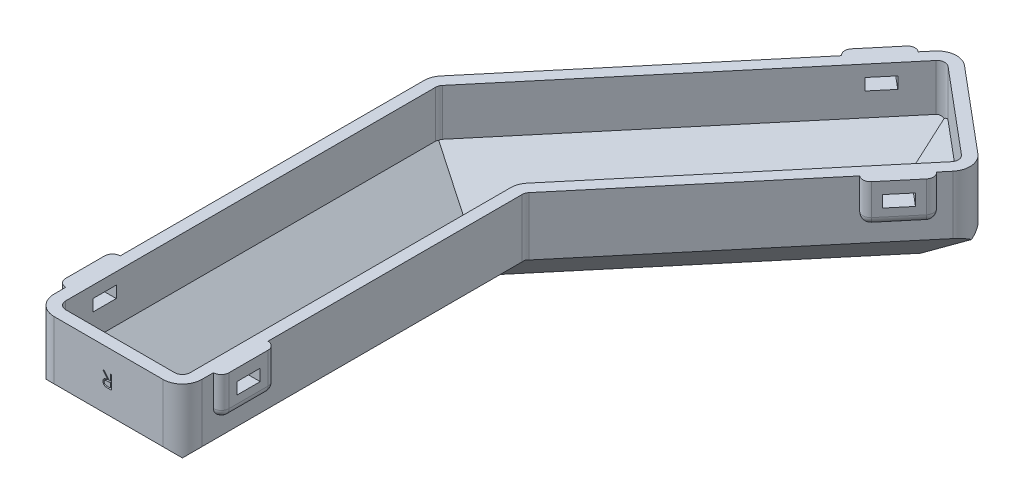
SolidWorks part; units mm, degrees
ref_plane "Front Plane" through (0, 0, 0) normal (0, 0, 1) x (1, 0, 0)
ref_plane "Top Plane" through (0, 0, 0) normal (0, 1, 0) x (1, 0, 0)
ref_plane "Right Plane" through (0, 0, 0) normal (1, 0, 0) x (0, 0, -1)
sketch "Sketch1" plane through (0, 0, 0) normal (0, 1, 0) x (1, 0, 0)
  line L0 (0, -95) -> (0, 0) construction
  line L1 (0, 0) -> (57.8509, 68.944) construction
  line L2 (19, -95) -> (19, -6.9154)
  line L3 (-19, -95) -> (-19, 6.9154)
  line L4 (-19, -95) -> (19, -95)
  line L5 (19, -6.9154) -> (72.4057, 56.731)
  line L6 (43.296, 81.157) -> (72.4057, 56.731)
  line L7 (43.296, 81.157) -> (-19, 6.9154)
  line L8 (43.6658, 76.9305) -> (68.1792, 56.3613) construction
  line L9 (43.6658, 76.9305) -> (-16, 5.8235) construction
  line L10 (-16, 5.8235) -> (-16, -92) construction
  line L11 (-16, -92) -> (16, -92) construction
  line L12 (16, -92) -> (16, -5.8235) construction
  line L13 (16, -5.8235) -> (68.1792, 56.3613) construction
  point P9 (0, -95)
  point P10 (57.8509, 68.944)
  point P12 (55.9225, 66.6459)
  point P13 (0, -92)
  dimension "D1" = 95
  dimension "D2" = 90
  dimension "D3" = 38
  dimension "D4" = 38
  dimension "D5" = 140
  dimension "D6" = 32
  dimension "D7" = 32
  dimension "D8" = 3
  dimension "D9" = 3
extrude "Boss-Extrude1" add sketch "Sketch1" along normal blind 25
sketch "Sketch2" plane through (0, 25, 0) normal (0, 1, 0) x (1, 0, 0)
  line L0 (43.6658, 76.9305) -> (68.1792, 56.3613)
  line L1 (43.6658, 76.9305) -> (-16, 5.8235)
  line L2 (-16, 5.8235) -> (-16, -92)
  line L3 (-16, -92) -> (16, -92)
  line L4 (16, -92) -> (16, -5.8235)
  line L5 (16, -5.8235) -> (68.1792, 56.3613)
  line L6 (0, 0) -> (57.8509, 68.944) construction
  line L7 (72.4057, 56.731) -> (43.296, 81.157) construction
  line L8 (0, 0) -> (0, -95) construction
  line L9 (-19, -95) -> (19, -95) construction
  point P0 (55.9225, 66.6459)
  point P1 (0, -92)
  dimension "D1" = 32
  dimension "D2" = 32
  dimension "D3" = 3
  dimension "D4" = 3
extrude "Cut-Extrude1" cut sketch "Sketch2" against normal blind 22
chamfer "Chamfer1" distance 10 angle 45 12 edges at (55.9225, 3, -66.6459) (42.0896, 3, -25.2689) (16, 3, 48.9118) (0, 3, 92) (-16, 3, 43.0882) (13.8329, 3, -41.377) (12.148, 0, -44.0362) (57.8509, 0, -68.944) (45.7029, 0, -24.9078) (19, 0, 50.9577) (-19, 0, 44.0423) (0, 0, 95)
fillet "Fillet1" radius 2 6 edges at (-16, 19, 92) (16, 19, 92) (-16, 19, -5.8235) (19, 17.5, 6.9154) (43.6658, 19, -76.9305) (68.1792, 19, -56.3613)
fillet "Fillet2" radius 5 6 edges at (-19, 17.5, 95) (19, 17.5, 95) (-19, 17.5, -6.9154) (16, 19, 5.8235) (72.4057, 17.5, -56.731) (43.296, 17.5, -81.157)
sketch "Sketch3" plane through (-14.5548, 0, -12.213) normal (-0.766, 0, -0.6428) x (-0.6428, 0, 0.766)
  line L0 (-85, 25) -> (5.0956, 25) construction
  line L1 (-68, 15) -> (-82, 15)
  line L2 (-68, 15) -> (-68, 25)
  line L3 (-68, 25) -> (-82, 25)
  line L4 (-82, 15) -> (-82, 25)
  line L5 (-68, 15) -> (-82, 25) construction
  line L6 (-68, 25) -> (-82, 15) construction
  line L7 (-85, 25) -> (-85, 10) construction
  point P0 (-75, 20)
  dimension "D1" = 10
  dimension "D2" = 14
  dimension "D3" = 3
extrude "Boss-Extrude2" add sketch "Sketch3" along normal blind 2
sketch "Sketch4" plane through (14.5548, 0, 12.213) normal (0.766, 0, 0.6428) x (0.6428, 0, -0.766)
  line L0 (7.6434, 25) -> (85, 25) construction
  line L1 (82, 15) -> (68, 15)
  line L2 (82, 15) -> (82, 25)
  line L3 (82, 25) -> (68, 25)
  line L4 (68, 15) -> (68, 25)
  line L5 (82, 15) -> (68, 25) construction
  line L6 (82, 25) -> (68, 15) construction
  line L7 (85, 10) -> (85, 25) construction
  point P0 (75, 20)
  dimension "D1" = 3
  dimension "D2" = 10
  dimension "D3" = 14
extrude "Boss-Extrude3" add sketch "Sketch4" along normal blind 2
sketch "Sketch5" plane through (16.0869, 0, 13.4985) normal (0.766, 0, 0.6428) x (0.6428, 0, -0.766)
  line L0 (82, 15) -> (82, 25) construction
  line L1 (78, 19) -> (72, 19)
  line L2 (78, 19) -> (78, 22)
  line L3 (78, 22) -> (72, 22)
  line L4 (72, 19) -> (72, 22)
  line L5 (78, 19) -> (72, 22) construction
  line L6 (78, 22) -> (72, 19) construction
  line L7 (82, 25) -> (68, 25) construction
  point P0 (75, 20.5)
  dimension "D1" = 4
  dimension "D2" = 3
  dimension "D3" = 3
  dimension "D4" = 6
extrude "Cut-Extrude2" cut sketch "Sketch5" against normal through all both and the other way through all
sketch "Sketch6" plane through (-19, 0, 0) normal (-1, 0, 0) x (0, 0, 1)
  line L0 (-5.0956, 25) -> (90, 25) construction
  line L1 (87, 15) -> (73, 15)
  line L2 (87, 15) -> (87, 25)
  line L3 (87, 25) -> (73, 25)
  line L4 (73, 15) -> (73, 25)
  line L5 (87, 15) -> (73, 25) construction
  line L6 (87, 25) -> (73, 15) construction
  line L7 (90, 10) -> (90, 25) construction
  point P0 (80, 20)
  dimension "D1" = 3
  dimension "D2" = 14
  dimension "D3" = 10
extrude "Boss-Extrude4" add sketch "Sketch6" along normal blind 2
sketch "Sketch7" plane through (19, 0, 0) normal (1, 0, 0) x (0, 0, -1)
  line L0 (-90, 25) -> (-7.6434, 25) construction
  line L1 (-73, 15) -> (-87, 15)
  line L2 (-73, 15) -> (-73, 25)
  line L3 (-73, 25) -> (-87, 25)
  line L4 (-87, 15) -> (-87, 25)
  line L5 (-73, 15) -> (-87, 25) construction
  line L6 (-73, 25) -> (-87, 15) construction
  line L7 (-90, 25) -> (-90, 10) construction
  point P0 (-80, 20)
  dimension "D1" = 10
  dimension "D2" = 14
  dimension "D3" = 3
extrude "Boss-Extrude5" add sketch "Sketch7" along normal blind 2
sketch "Sketch8" plane through (21, 0, 0) normal (1, 0, 0) x (0, 0, -1)
  line L0 (-73, 25) -> (-87, 25) construction
  line L1 (-77, 19) -> (-83, 19)
  line L2 (-77, 19) -> (-77, 22)
  line L3 (-77, 22) -> (-83, 22)
  line L4 (-83, 19) -> (-83, 22)
  line L5 (-77, 19) -> (-83, 22) construction
  line L6 (-77, 22) -> (-83, 19) construction
  line L7 (-73, 15) -> (-73, 25) construction
  point P0 (-80, 20.5)
  dimension "D1" = 6
  dimension "D2" = 3
  dimension "D3" = 3
  dimension "D4" = 4
extrude "Cut-Extrude3" cut sketch "Sketch8" against normal through all both and the other way through all
fillet "Fillet4" radius 2 12 edges at (-21, 20, 87) (-21, 15, 80) (-21, 20, 73) (27.6226, 20, -65.5896) (36.6217, 20, -76.3142) (32.1221, 15, -70.9519) (68.7955, 20, -49.3171) (59.7965, 20, -38.5925) (64.296, 15, -43.9548) (21, 20, 73) (21, 20, 87) (21, 15, 80)
sketch "Sketch9" plane through (0, 0, 95) normal (0, 0, 1) x (1, 0, 0)
  line L0 (0, 10) -> (0, 25) construction
  line L1 (-14, 10) -> (14, 10) construction
  line L2 (-14, 25) -> (14, 25) construction
  line L3 (14, 17.5) -> (-14, 17.5) construction
  line L4 (14, 10) -> (14, 25) construction
  line L5 (-14, 25) -> (-14, 10) construction
  text T0 "<r180>R</r>"
  point P7 (1.2189, 19.4499)
  point P8 (0, 0)
  point P9 (0, 0)
extrude "Cut-Extrude4" cut sketch "Sketch9" against normal blind 0.5
